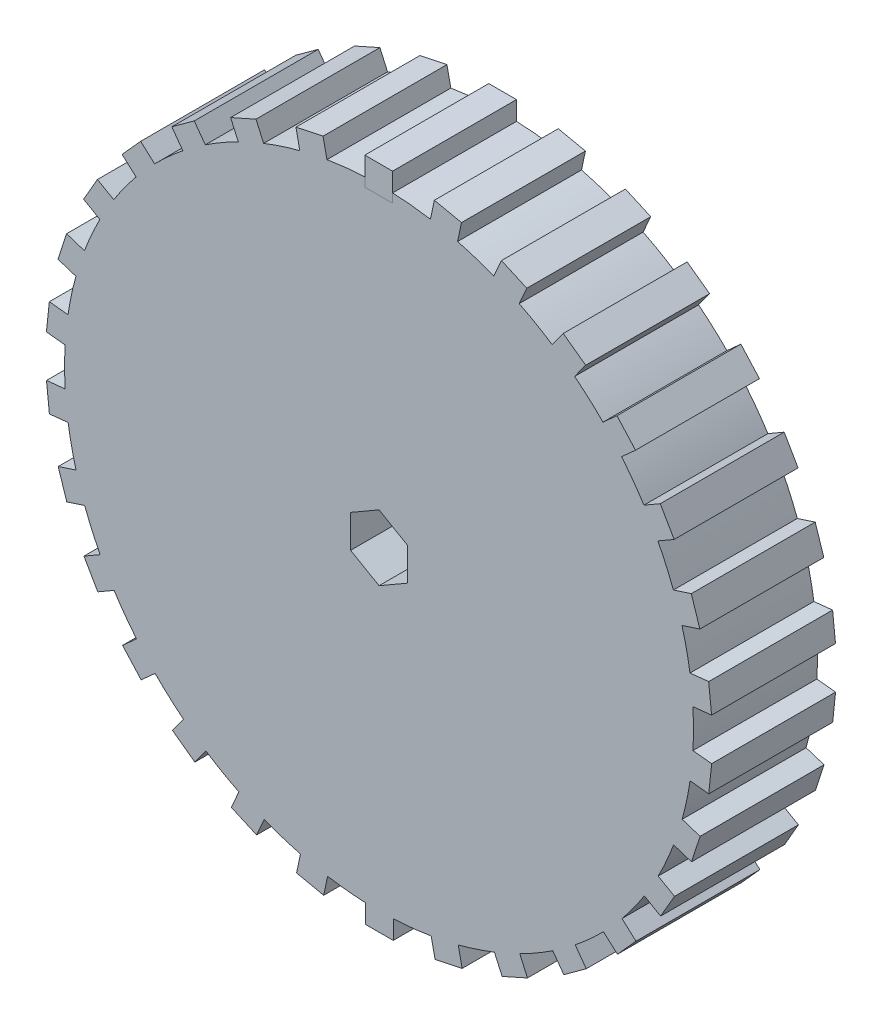
SolidWorks part; units mm, degrees
ref_plane "Front Plane" through (0, 0, 0) normal (0, 0, 1) x (1, 0, 0)
ref_plane "Top Plane" through (0, 0, 0) normal (0, 1, 0) x (1, 0, 0)
ref_plane "Right Plane" through (0, 0, 0) normal (1, 0, 0) x (0, 0, -1)
sketch "Sketch1" plane through (0, 0, 0) normal (0, 0, 1) x (1, 0, 0)
  circle A0 centre (0, 0) radius 34
  dimension "D1" = 68
extrude "Boss-Extrude1" add sketch "Sketch1" along normal blind 13.4
sketch "Sketch2" plane through (0, 0, 13.4) normal (0, 0, 1) x (1, 0, 0)
  line L1 (0, -3.5507) -> (3.075, -1.7754)
  line L2 (3.075, -1.7754) -> (3.075, 1.7754)
  line L3 (3.075, 1.7754) -> (0, 3.5507)
  line L4 (0, 3.5507) -> (-3.075, 1.7754)
  line L5 (-3.075, 1.7754) -> (-3.075, -1.7754)
  line L6 (-3.075, -1.7754) -> (0, -3.5507)
  circle A0 centre (0, 0) radius 3.075 construction
  dimension "D1" = 6.15
extrude "Cut-Extrude1" cut sketch "Sketch2" against normal up to next
sketch "Sketch3" plane through (0, 0, 0) normal (0, 0, -1) x (-1, 0, 0)
  circle A0 centre (0, 0) radius 3.5507
extrude "Cut-Extrude3" [suppressed] cut sketch "Sketch3" against normal blind 5.5
sketch "Sketch4" plane through (0, 0, 13.4) normal (0, 0, 1) x (1, 0, 0)
  circle A0 centre (0, 22.5) radius 10
  dimension "D1" = 20
  dimension "D2" = 22.5
extrude "Cut-Extrude4" [suppressed] cut sketch "Sketch4" against normal up to next
sketch "Sketch6" plane through (0, 0, 0) normal (1, 0, 0) x (0, 0, -1)
  line L0 (-13.4, 0) -> (2.0132, 0) construction
  line L1 (-13.4, 34) -> (-13.4, -34) construction
pattern_circular "CirPattern4" [suppressed] count 5 over 360 of bodies 105
sketch "Sketch9" plane through (0, 0, 0) normal (0, 1, 0) x (1, 0, 0)
  line L0 (-3.075, -13.4) -> (0, -13.4) construction
  line L1 (-1.5375, -13.4) -> (1.4625, -13.4)
  line L2 (-1.5375, -13.4) -> (-1.5375, 0)
  line L3 (-1.5375, 0) -> (1.4625, 0)
  line L4 (1.4625, -13.4) -> (1.4625, 0)
  line L5 (34, 0) -> (-34, 0) construction
  dimension "D1" = 3
extrude "Boss-Extrude3" add sketch "Sketch9" along normal blind 3 from offset 33 separate body
pattern_circular "CirPattern11" count 30 over 360 about axis through (0, 0, 13.4) along (0, 0, -1) of "Boss-Extrude3"
sketch "Sketch10" [suppressed] plane through (0, 0, 0) normal (0, 0, -1) x (-1, 0, 0)
  circle A0 centre (0, 0) radius 4.7507
  circle A1 centre (0, 0) radius 3.5507 construction
  dimension "D1" = 1.2
extrude "Boss-Extrude4" [suppressed] add sketch "Sketch10" along normal blind 1.6
sketch "Sketch11" [suppressed] plane through (0, 0, -1.6) normal (0, 0, -1) x (-1, 0, 0)
  circle A0 centre (0, 0) radius 3.55
  dimension "D1" = 7.1
extrude "Cut-Extrude5" [suppressed] cut sketch "Sketch11" against normal up to next
sketch "Sketch12" plane through (0, 0, 0) normal (0, 0, -1) x (-1, 0, 0)
  circle A0 centre (0, 0) radius 29
  circle A1 centre (0, 0) radius 7
  arc A2 (26.2221, -21.6425) -> (28.646, -18.3141) centre (0, 0) ccw construction
  dimension "D1" = 5
  dimension "D2" = 14
extrude "Cut-Extrude6" cut sketch "Sketch12" against normal blind 6.7
sketch "Sketch14" plane through (0, 0, 0) normal (0, 0, -1) x (-1, 0, 0)
  circle A0 centre (0, 0) radius 7.8691
extrude "Cut-Extrude7" cut sketch "Sketch14" against normal blind 2
fillet "Fillet1" radius 10 1 edges at (-29, 0, 6.7)
